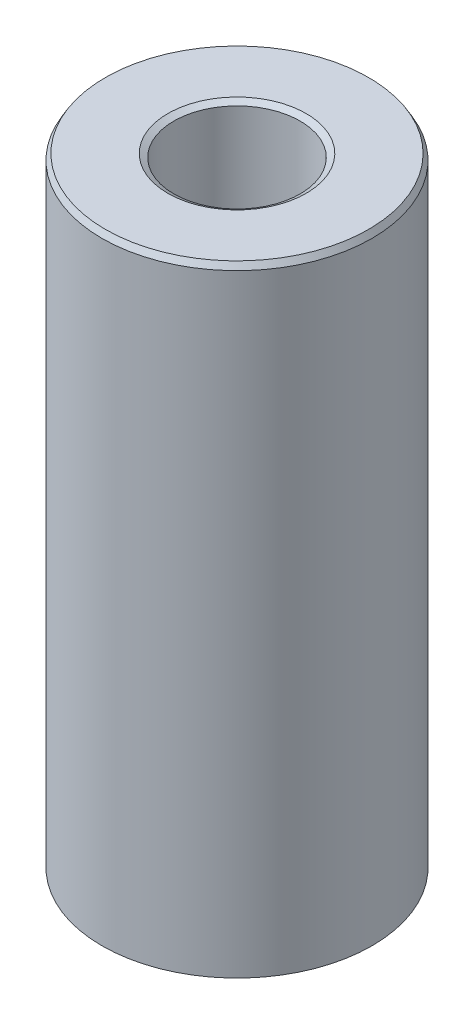
SolidWorks part; units mm, degrees
ref_plane "Front Plane" through (0, 0, 0) normal (0, 0, 1) x (1, 0, 0)
ref_plane "Top Plane" through (0, 0, 0) normal (0, 1, 0) x (1, 0, 0)
ref_plane "Right Plane" through (0, 0, 0) normal (1, 0, 0) x (0, 0, -1)
sketch "Sketch1" plane through (0, 0, 0) normal (0, 1, 0) x (1, 0, 0)
  circle A0 centre (0, 0) radius 50
  dimension "SLEEVE_OD" = 100
extrude "Boss-Extrude1" add sketch "Sketch1" along normal blind 230.2932
sketch "Sketch2" plane through (0, 0, 0) normal (0, 1, 0) x (1, 0, 0)
  circle A0 centre (0, 0) radius 23.3802
  dimension "BORE_D" = 46.7603
extrude "Cut-Extrude1" cut sketch "Sketch2" along normal through all
chamfer "Chamfer1" distance 2.2256 angle 30 4 edges at (0, 230.2932, 23.3802) (0, 0, 23.3802) (0, 0, 50) (0, 230.2932, 50) first distance on face at (0, 230.2932, 23.3802) first distance on face at (0, 0, 23.3802) first distance on face at (0, 230.2932, 50)
